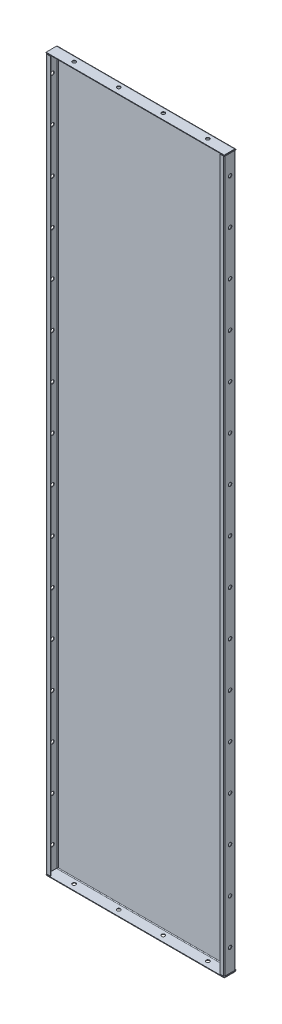
SolidWorks part; units mm, degrees
note: The reader was unsure of these and kept them because the rebuilt part matched: flange length of "Edge-Flange5", "Edge-Flange1", "Edge-Flange3".
material "Galvanized Steel"
ref_plane "Front Plane" through (0, 0, 0) normal (0, 0, 1) x (1, 0, 0)
ref_plane "Top Plane" through (0, 0, 0) normal (0, 1, 0) x (1, 0, 0)
ref_plane "Right Plane" through (0, 0, 0) normal (1, 0, 0) x (0, 0, -1)
sketch "Sketch1" plane through (0, 0, 0) normal (0, 0, 1) x (1, 0, 0)
  line L1 (304, -1216) -> (-304, -1216)
  line L2 (304, -1216) -> (304, 1216)
  line L3 (304, 1216) -> (-304, 1216)
  line L4 (-304, -1216) -> (-304, 1216)
  line L5 (304, -1216) -> (-304, 1216) construction
  line L6 (304, 1216) -> (-304, -1216) construction
  point P0 (0, 0)
  dimension "D1" = 608
  dimension "D2" = 2432
base flange "Base-Flange1" sketch "Sketch1" thickness 2 reverse thickness direction no parameters "D1"=0.7366
edge flange "Edge-Flange5" sketch "Sketch48" flange profiles "Sketch48", "Sketch49" flange angle 90 flange length 40 flange position material inside bend radius 2.5 thickness 2 relief rectangular parameters "D6"=10, "D8"=1
sketch "Sketch48" plane through (0, 1216, 0) normal (0, 1, 0) x (-1, 0, 0)
  line L0 (-304, 0) -> (304, 0) construction
  line L1 (-304, 0) -> (304, 0)
  line L2 (-304, 0) -> (-304, 38)
  line L3 (-304, 38) -> (304, 38)
  line L4 (304, 38) -> (304, 0)
sketch "Sketch49" plane through (0, -1216, 0) normal (0, -1, 0) x (1, 0, 0)
  line L0 (-304, 0) -> (304, 0) construction
  line L1 (-304, 0) -> (304, 0)
  line L2 (-304, 0) -> (-304, 38)
  line L3 (-304, 38) -> (304, 38)
  line L4 (304, 38) -> (304, 0)
bend "EdgeBend13" bend radius 2.5 bend angle 90 parameters "D5"=1
bend "EdgeBend14" bend radius 2.5 bend angle 90 parameters "D5"=2
edge flange "Edge-Flange1" sketch "Sketch14" flange profiles "Sketch14", "Sketch17" flange angle 90 flange length 40 flange position material inside bend radius 2.5 thickness 2 parameters "D6"=10, "D8"=1
sketch "Sketch14" plane through (304, 0, 0) normal (1, 0, 0) x (0, 1, 0)
  line L0 (-1211.5, 0) -> (1211.5, 0) construction
  line L1 (-1211.5, 0) -> (1211.5, 0)
  line L2 (-1211.5, 0) -> (-1211.5, 38)
  line L3 (-1211.5, 38) -> (1211.5, 38)
  line L4 (1211.5, 38) -> (1211.5, 0)
sketch "Sketch17" plane through (-304, 0, 0) normal (-1, 0, 0) x (0, -1, 0)
  line L0 (-1211.5, 0) -> (1211.5, 0) construction
  line L1 (-1211.5, 0) -> (1211.5, 0)
  line L2 (-1211.5, 0) -> (-1211.5, 38)
  line L3 (-1211.5, 38) -> (1211.5, 38)
  line L4 (1211.5, 38) -> (1211.5, 0)
bend "EdgeBend1" bend radius 2.5 bend angle 90 parameters "D5"=1
bend "EdgeBend4" bend radius 2.5 bend angle 90 parameters "D5"=4
edge flange "Edge-Flange3" sketch "Sketch33" flange profiles "Sketch33", "Sketch34" flange angle 90 flange length 15 flange position material inside bend radius 0.7366 thickness 2 relief rectangular parameters "D6"=10, "D8"=1
sketch "Sketch33" plane through (302, 0, 38) normal (0, 0, 1) x (0, 1, 0)
  line L0 (1211.5, 0) -> (-1211.5, 0) construction
  line L1 (1211.5, 0) -> (-1211.5, 0)
  line L2 (-1211.5, 0) -> (-1211.5, 13)
  line L3 (-1211.5, 13) -> (1211.5, 13)
  line L4 (1211.5, 13) -> (1211.5, 0)
sketch "Sketch34" plane through (-302, 0, 38) normal (0, 0, 1) x (0, -1, 0)
  line L0 (1211.5, 0) -> (-1211.5, 0) construction
  line L1 (1211.5, 0) -> (-1211.5, 0)
  line L2 (-1211.5, 0) -> (-1211.5, 13)
  line L3 (-1211.5, 13) -> (1211.5, 13)
  line L4 (1211.5, 13) -> (1211.5, 0)
bend "EdgeBend9" bend radius 0.7366 bend angle 90 parameters "D5"=7
bend "EdgeBend10" bend radius 0.7366 bend angle 90 parameters "D5"=8
sketch "Sketch35" plane through (304, 0, 0) normal (1, 0, 0) x (0, 0, -1)
  line L1 (2, 1211.5) -> (2, -1211.5) construction
  line L2 (-35.2634, -1211.5) -> (-2.5, -1211.5) construction
  circle A0 centre (-18, -1135.5) radius 6
  dimension "D1" = 76
  dimension "D2" = 12
  dimension "D3" = 20
extrude "Cut-Extrude1" cut sketch "Sketch35" against normal through all normal cut yes
pattern_linear "LPattern1" count 16 spacing 152 along (0, 1, 0) of "Cut-Extrude1"
sketch "Sketch37" plane through (0, 1216, -1216) normal (0, -1, 0) x (1, 0, 0)
  line L1 (304, 1254) -> (304, 1218.5) construction
  line L3 (-299.5, 1214) -> (299.5, 1214) construction
  circle A0 centre (228, 1234) radius 6
  dimension "D1" = 76
  dimension "D2" = 12
  dimension "D3" = 20
extrude "Cut-Extrude3" cut sketch "Sketch37" along normal through all normal cut yes
pattern_linear "LPattern3" count 4 spacing 152 along (-1, 0, 0) of "Cut-Extrude3"
sketch "Bend-Lines1" [suppressed] plane through (0, 0, 0) normal (0, 1, 0) x (1, 0, 0)
sketch "Bounding-Box1" [suppressed] plane through (0, 0, 0) normal (0, 1, 0) x (1, 0, 0)
sheet metal parameters "Sheet-Metal1" thickness 2 parameters "D1"=0.7366
flat pattern "Flat-Pattern1" [suppressed]
sketch "Bend-Lines2" plane through (0, 0, 0) normal (0, 1, 0) x (1, 0, 0)
sketch3d "Bounding-Box2" [suppressed]
  line L0 (304, 1216, 0) -> (304, -1216, 0) construction
  line L1 (-304, 1216, 0) -> (-304, -1216, 0) construction
  line L2 (304, 1216, 0) -> (-304, 1216, 0) construction
  line L3 (304, -1216, 0) -> (-304, -1216, 0) construction
sheet metal parameters "Sheet-Metal2" thickness 2 parameters "D1"=0.7366
flat pattern "Flat-Pattern1" [suppressed]
sketch "Bend-Lines2" plane through (0, 0, 0) normal (0, 0, 1) x (1, 0, 0)
  line L0 (-302.2489, 1216) -> (-302.2489, -1216) construction
  line L3 (302.2489, -1216) -> (302.2489, 1216) construction
  line L4 (-302.2489, 1216) -> (-302.2489, -1216) construction
  line L7 (302.2489, -1216) -> (302.2489, 1216) construction
sketch3d "Bounding-Box2" [suppressed]
  line L0 (338.4978, 1216, 0) -> (338.4978, -1216, 0) construction
  line L1 (-338.4978, 1216, 0) -> (-338.4978, -1216, 0) construction
  line L2 (338.4978, 1216, 0) -> (-338.4978, 1216, 0) construction
  line L3 (338.4978, -1216, 0) -> (-338.4978, -1216, 0) construction
bend of the flat pattern "Flatten-<EdgeBend1>1"
bend of the flat pattern "Flatten-<EdgeBend4>1"
bend of the flat pattern "Flatten-<EdgeBend14>2"
bend of the flat pattern "Flatten-<EdgeBend13>2"
sheet metal parameters "Sheet-Metal7" thickness 2 parameters "D1"=0.7366
flat pattern "Flat-Pattern1" [suppressed]
sketch "Bend-Lines2" plane through (0, 0, 0) normal (0, 0, 1) x (1, 0, 0)
  line L0 (-302.2489, 1216) -> (-302.2489, -1216) construction
  line L3 (302.2489, -1216) -> (302.2489, 1216) construction
  line L4 (-302.2489, 1216) -> (-302.2489, -1216) construction
  line L7 (302.2489, -1216) -> (302.2489, 1216) construction
  line L8 (-337.1251, 1216) -> (-337.1251, -1216) construction
  line L9 (337.1251, -1216) -> (337.1251, 1216) construction
  line L10 (-337.1251, 1216) -> (-337.1251, -1216) construction
  line L11 (337.1251, -1216) -> (337.1251, 1216) construction
  point P2 (-299.7929, -1248.2489)
  point P3 (299.7929, -1248.2489)
  point P4 (299.7929, 1248.2489)
  point P5 (-299.7929, 1248.2489)
sketch3d "Bounding-Box2" [suppressed]
  line L0 (350.7524, 1216, 0) -> (350.7524, -1216, 0) construction
  line L1 (-350.7524, 1216, 0) -> (-350.7524, -1216, 0) construction
  line L2 (350.7524, 1216, 0) -> (-350.7524, 1216, 0) construction
  line L3 (350.7524, -1216, 0) -> (-350.7524, -1216, 0) construction
bend of the flat pattern "Flatten-<EdgeBend1>1"
bend of the flat pattern "Flatten-<EdgeBend4>1"
bend of the flat pattern "Flatten-<EdgeBend9>1"
bend of the flat pattern "Flatten-<EdgeBend10>1"
bend of the flat pattern "Flatten-<EdgeBend14>3"
bend of the flat pattern "Flatten-<EdgeBend13>3"
sheet metal parameters "Sheet-Metal8" thickness 2 parameters "D1"=0.7366
flat pattern "Flat-Pattern1" [suppressed]
sketch "Bend-Lines2" plane through (0, 0, 0) normal (0, 0, 1) x (1, 0, 0)
  line L0 (-300.7489, 1247.2929) -> (-300.7489, -1247.2929) construction
  line L1 (-299.7929, -1248.2489) -> (299.7929, -1248.2489) construction
  line L2 (299.7929, 1248.2489) -> (-299.7929, 1248.2489) construction
  line L3 (300.7489, -1247.2929) -> (300.7489, 1247.2929) construction
  line L4 (-300.7489, 1247.2929) -> (-300.7489, -1247.2929) construction
  line L5 (-299.7929, -1248.2489) -> (299.7929, -1248.2489) construction
  line L6 (299.7929, 1248.2489) -> (-299.7929, 1248.2489) construction
  line L7 (300.7489, -1247.2929) -> (300.7489, 1247.2929) construction
  line L8 (-334.6251, 1247.2929) -> (-334.6251, -1247.2929) construction
  line L9 (334.6251, -1247.2929) -> (334.6251, 1247.2929) construction
  line L10 (-334.6251, 1247.2929) -> (-334.6251, -1247.2929) construction
  line L11 (334.6251, -1247.2929) -> (334.6251, 1247.2929) construction
sketch3d "Bounding-Box2" [suppressed]
  line L0 (348.2524, 1283.4978, 0) -> (348.2524, -1283.4978, 0) construction
  line L1 (-348.2524, 1283.4978, 0) -> (-348.2524, -1283.4978, 0) construction
  line L2 (348.2524, 1283.4978, 0) -> (-348.2524, 1283.4978, 0) construction
  line L3 (348.2524, -1283.4978, 0) -> (-348.2524, -1283.4978, 0) construction
bend of the flat pattern "Flatten-<EdgeBend1>1"
bend of the flat pattern "Flatten-<EdgeBend4>1"
bend of the flat pattern "Flatten-<EdgeBend9>1"
bend of the flat pattern "Flatten-<EdgeBend10>1"
bend of the flat pattern "Flatten-<EdgeBend14>4"
bend of the flat pattern "Flatten-<EdgeBend13>4"
sheet metal parameters "Sheet-Metal9" thickness 2 parameters "D1"=0.7366
flat pattern "Flat-Pattern1" [suppressed]
sketch "Bend-Lines2" plane through (0, 0, 0) normal (0, 0, 1) x (1, 0, 0)
  line L0 (-300.7489, 1247.2929) -> (-300.7489, -1247.2929) construction
  line L1 (-299.7929, -1248.2489) -> (299.7929, -1248.2489) construction
  line L2 (299.7929, 1248.2489) -> (-299.7929, 1248.2489) construction
  line L3 (300.7489, -1247.2929) -> (300.7489, 1247.2929) construction
  line L4 (-300.7489, 1247.2929) -> (-300.7489, -1247.2929) construction
  line L5 (-299.7929, -1248.2489) -> (299.7929, -1248.2489) construction
  line L6 (299.7929, 1248.2489) -> (-299.7929, 1248.2489) construction
  line L7 (300.7489, -1247.2929) -> (300.7489, 1247.2929) construction
  line L8 (-334.6251, 1247.2929) -> (-334.6251, -1247.2929) construction
  line L9 (334.6251, -1247.2929) -> (334.6251, 1247.2929) construction
  line L10 (-334.6251, 1247.2929) -> (-334.6251, -1247.2929) construction
  line L11 (334.6251, -1247.2929) -> (334.6251, 1247.2929) construction
sketch3d "Bounding-Box2" [suppressed]
  line L0 (348.2524, 1283.4978, 0) -> (348.2524, -1283.4978, 0) construction
  line L1 (-348.2524, 1283.4978, 0) -> (-348.2524, -1283.4978, 0) construction
  line L2 (348.2524, 1283.4978, 0) -> (-348.2524, 1283.4978, 0) construction
  line L3 (348.2524, -1283.4978, 0) -> (-348.2524, -1283.4978, 0) construction
bend of the flat pattern "Flatten-<EdgeBend1>1"
bend of the flat pattern "Flatten-<EdgeBend4>1"
bend of the flat pattern "Flatten-<EdgeBend9>1"
bend of the flat pattern "Flatten-<EdgeBend10>1"
bend of the flat pattern "Flatten-<EdgeBend14>5"
bend of the flat pattern "Flatten-<EdgeBend13>5"
sheet metal parameters "Sheet-Metal12" thickness 2 parameters "D1"=0.7366
flat pattern "Flat-Pattern1" [suppressed]
sketch "Bend-Lines2" plane through (0, 0, 0) normal (0, 0, 1) x (1, 0, 0)
  line L0 (-302.2489, 1213.2929) -> (-302.2489, -1213.2929) construction
  line L1 (-301.2929, -1214.2489) -> (301.2929, -1214.2489) construction
  line L2 (301.2929, 1214.2489) -> (-301.2929, 1214.2489) construction
  line L3 (302.2489, -1213.2929) -> (302.2489, 1213.2929) construction
  line L4 (-302.2489, 1213.2929) -> (-302.2489, -1213.2929) construction
  line L5 (-301.2929, -1214.2489) -> (301.2929, -1214.2489) construction
  line L6 (301.2929, 1214.2489) -> (-301.2929, 1214.2489) construction
  line L7 (302.2489, -1213.2929) -> (302.2489, 1213.2929) construction
  line L8 (-336.1251, 1213.2929) -> (-336.1251, -1213.2929) construction
  line L9 (336.1251, -1213.2929) -> (336.1251, 1213.2929) construction
  line L10 (-336.1251, 1213.2929) -> (-336.1251, -1213.2929) construction
  line L11 (336.1251, -1213.2929) -> (336.1251, 1213.2929) construction
sketch3d "Bounding-Box2" [suppressed]
  line L0 (349.7524, 1249.4978, 0) -> (349.7524, -1249.4978, 0) construction
  line L1 (-349.7524, 1249.4978, 0) -> (-349.7524, -1249.4978, 0) construction
  line L2 (349.7524, 1249.4978, 0) -> (-349.7524, 1249.4978, 0) construction
  line L3 (349.7524, -1249.4978, 0) -> (-349.7524, -1249.4978, 0) construction
bend of the flat pattern "Flatten-<EdgeBend1>1"
bend of the flat pattern "Flatten-<EdgeBend4>1"
bend of the flat pattern "Flatten-<EdgeBend9>1"
bend of the flat pattern "Flatten-<EdgeBend10>1"
bend of the flat pattern "Flatten-<EdgeBend14>6"
bend of the flat pattern "Flatten-<EdgeBend13>6"
sheet metal parameters "Sheet-Metal13" thickness 2 parameters "D1"=0.7366
flat pattern "Flat-Pattern1"
sketch "Bend-Lines2" plane through (0, 0, 0) normal (0, 0, 1) x (1, 0, 0)
  line L0 (-302.2489, 1211.5) -> (-302.2489, -1211.5) construction
  line L3 (302.2489, -1211.5) -> (302.2489, 1211.5) construction
  line L4 (-302.2489, 1211.5) -> (-302.2489, -1211.5) construction
  line L7 (302.2489, -1211.5) -> (302.2489, 1211.5) construction
  line L8 (-339.1251, 1211.5) -> (-339.1251, -1211.5) construction
  line L9 (339.1251, -1211.5) -> (339.1251, 1211.5) construction
  line L10 (-339.1251, 1211.5) -> (-339.1251, -1211.5) construction
  line L11 (339.1251, -1211.5) -> (339.1251, 1211.5) construction
  line L12 (-304, -1214.2489) -> (304, -1214.2489) construction
  line L13 (304, 1214.2489) -> (-304, 1214.2489) construction
  line L14 (-304, -1214.2489) -> (304, -1214.2489) construction
  line L15 (304, 1214.2489) -> (-304, 1214.2489) construction
sketch3d "Bounding-Box2" [suppressed]
  line L0 (352.7524, 1252.4978, 0) -> (352.7524, -1252.4978, 0) construction
  line L1 (-352.7524, 1252.4978, 0) -> (-352.7524, -1252.4978, 0) construction
  line L2 (352.7524, 1252.4978, 0) -> (-352.7524, 1252.4978, 0) construction
  line L3 (352.7524, -1252.4978, 0) -> (-352.7524, -1252.4978, 0) construction
bend of the flat pattern "Flatten-<EdgeBend1>1"
bend of the flat pattern "Flatten-<EdgeBend4>1"
bend of the flat pattern "Flatten-<EdgeBend9>1"
bend of the flat pattern "Flatten-<EdgeBend10>1"
bend of the flat pattern "Flatten-<EdgeBend14>7"
bend of the flat pattern "Flatten-<EdgeBend13>7"
sheet metal parameters "Sheet-Metal16" thickness 2 parameters "D1"=0.7366
flat pattern "Flat-Pattern1"
sketch "Bend-Lines2" plane through (0, 0, 0) normal (0, 0, 1) x (1, 0, 0)
  line L0 (-304, -1214.2489) -> (304, -1214.2489) construction
  line L1 (304, 1214.2489) -> (-304, 1214.2489) construction
  line L2 (-304, -1214.2489) -> (304, -1214.2489) construction
  line L3 (304, 1214.2489) -> (-304, 1214.2489) construction
sketch3d "Bounding-Box2" [suppressed]
  line L0 (304, 1250.4978, 0) -> (304, -1250.4978, 0) construction
  line L1 (-304, 1250.4978, 0) -> (-304, -1250.4978, 0) construction
  line L2 (304, 1250.4978, 0) -> (-304, 1250.4978, 0) construction
  line L3 (304, -1250.4978, 0) -> (-304, -1250.4978, 0) construction
bend of the flat pattern "Flatten-<EdgeBend13>1"
bend of the flat pattern "Flatten-<EdgeBend14>1"
